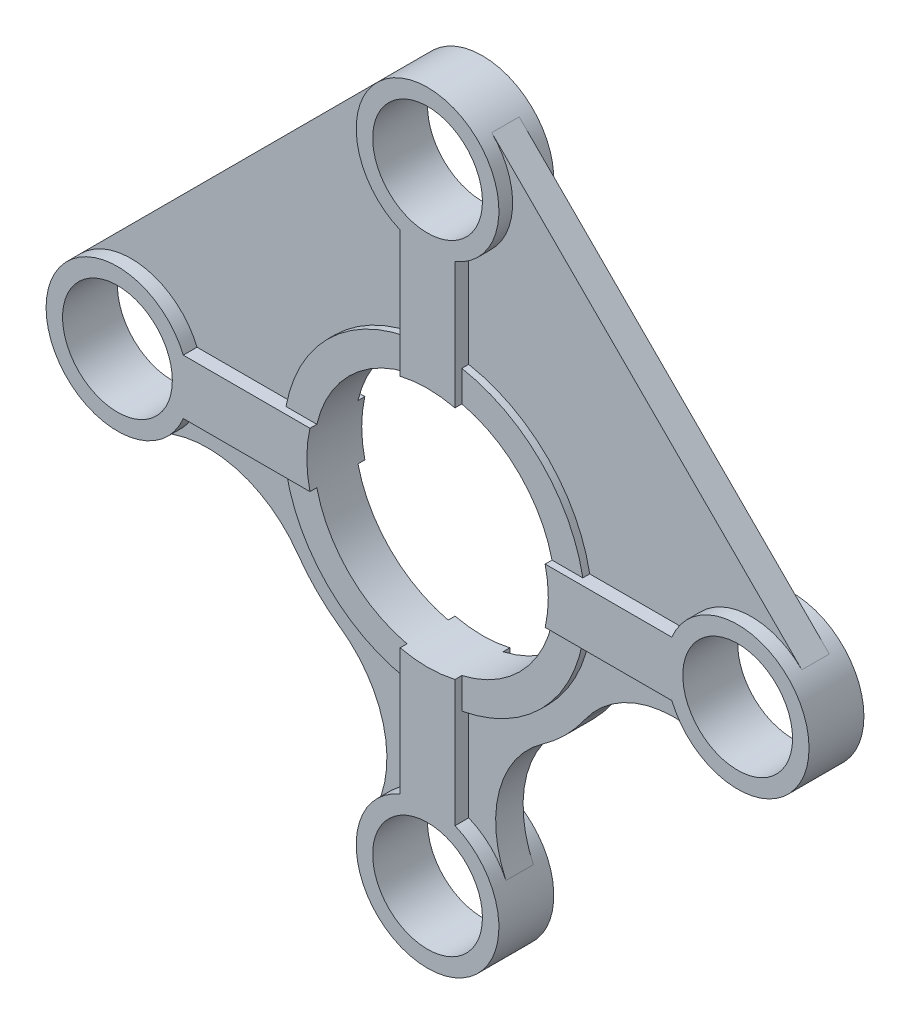
SolidWorks part; units mm, degrees
ref_plane "Front Plane" through (0, 0, 0) normal (0, 0, 1) x (1, 0, 0)
ref_plane "Top Plane" through (0, 0, 0) normal (0, 1, 0) x (1, 0, 0)
ref_plane "Right Plane" through (0, 0, 0) normal (1, 0, 0) x (0, 0, -1)
sketch "Sketch1" plane through (0, 0, 0) normal (0, 0, 1) x (1, 0, 0)
  line L0 (0, 0) -> (0, 115608.1768) construction
  line L1 (0, 0) -> (115608.1768, 0) construction
  line L2 (-42.8486, 10) -> (-95.6795, 10)
  line L3 (-42.8486, -10) -> (-95.6795, -10)
  line L4 (10, 42.8486) -> (10, 95.6795)
  line L5 (-10, 42.8486) -> (-10, 95.6795)
  line L6 (42.8486, -10) -> (95.6795, -10)
  line L7 (42.8486, 10) -> (95.6795, 10)
  line L8 (-10, -42.8486) -> (-10, -95.6795)
  line L9 (10, -42.8486) -> (10, -95.6795)
  line L10 (-18.3848, 131.3848) -> (-131.3848, 18.3848)
  line L11 (18.3848, 131.3848) -> (131.3848, 18.3848)
  circle A0 centre (0, 0) radius 44
  arc A1 (-54.0833, -10) -> (-10, -54.0833) centre (0, 0) ccw
  circle A2 centre (0, 0) radius 113 construction
  arc A3 (-89, 10) -> (-89, -10) centre (-113, 0) ccw
  circle A4 centre (-113, 0) radius 20
  arc A5 (10, 89) -> (-10, 89) centre (0, 113) ccw
  circle A6 centre (0, 113) radius 20
  arc A7 (89, -10) -> (89, 10) centre (113, 0) ccw
  circle A8 centre (113, 0) radius 20
  arc A9 (-10, -89) -> (10, -89) centre (0, -113) ccw
  circle A10 centre (0, -113) radius 20
  arc A11 (36.8034, -52.3594) -> (52.3594, -36.8034) centre (0, 0) ccw
  arc A12 (-23.5598, -102.0028) -> (-36.8034, -52.3594) centre (-59.8055, -85.0841) ccw
  arc A13 (-102.0028, -23.5598) -> (-52.3594, -36.8034) centre (-85.0841, -59.8055) cw
  arc A14 (23.5598, -102.0028) -> (36.8034, -52.3594) centre (59.8055, -85.0841) cw
  arc A15 (102.0028, -23.5598) -> (52.3594, -36.8034) centre (85.0841, -59.8055) ccw
  arc A16 (-52.3594, -36.8034) -> (-36.8034, -52.3594) centre (0, 0) ccw
  arc A17 (54.0833, 10) -> (10, 54.0833) centre (0, 0) ccw
  arc A18 (10, -54.0833) -> (54.0833, -10) centre (0, 0) ccw
  arc A19 (-10, 54.0833) -> (-54.0833, 10) centre (0, 0) ccw
  point P40 (0, 0)
  dimension "D1" = 88
  dimension "D2" = 110
  dimension "D3" = 226
  dimension "D4" = 40
  dimension "D5" = 52
  dimension "D7" = 128
  dimension "D8" = 4
  dimension "D9" = 40
  dimension "D10" = 40
  dimension "D6" = 20
extrude "Boss-Extrude1" add sketch "Sketch1" along normal mid plane 20 contours A6 L5 A0 L4 | A4 L3 A0 L2 | A10 L9 A0 L8 | A8 L7 A0 L6 | A6 L4 A5 L5 | A4 L2 A3 L3 | A8 L6 A7 L7 | A10 L8 A9 L9 region at (-68.748, 0, 0) region at (0, 68.748, 0) region at (-92.3397, 10.7214, 0) region at (0, -68.748, 0) region at (-24.798, 108.0943, 0) region at (68.748, 0, 0) region at (-10.7214, -92.3397, 0) region at (108.0943, 24.798, 0)
extrude "Boss-Extrude2" add sketch "Sketch1<3>" along normal mid plane 15 contours L5 A19 L2 A0 | L7 A17 L4 A0 | L9 A18 L6 A0 | L3 A1 L8 A0 region at (-33.2351, 33.2351, 0) region at (-33.2351, -33.2351, 0) region at (33.2351, 33.2351, 0) region at (33.2351, -33.2351, 0)
sketch "Sketch1<3>" plane through (0, 0, 0) normal (0, 0, 1) x (1, 0, 0) same geometry as "Sketch1"
extrude "Boss-Extrude3" add sketch "Sketch1<4>" along normal mid plane 10 contours A19 L5 A5 L10 A3 L2 | A17 L7 A7 L11 A5 L4 | A13 A16 A12 A9 L8 A1 L3 A3 | A18 L9 A9 A14 A11 A15 A7 L6 region at (-57.0044, 57.0044, 0) region at (-43.0084, -43.0084, 0) region at (57.0044, 57.0044, 0) region at (43.0084, -43.0084, 0)
sketch "Sketch1<4>" plane through (0, 0, 0) normal (0, 0, 1) x (1, 0, 0) same geometry as "Sketch1"
